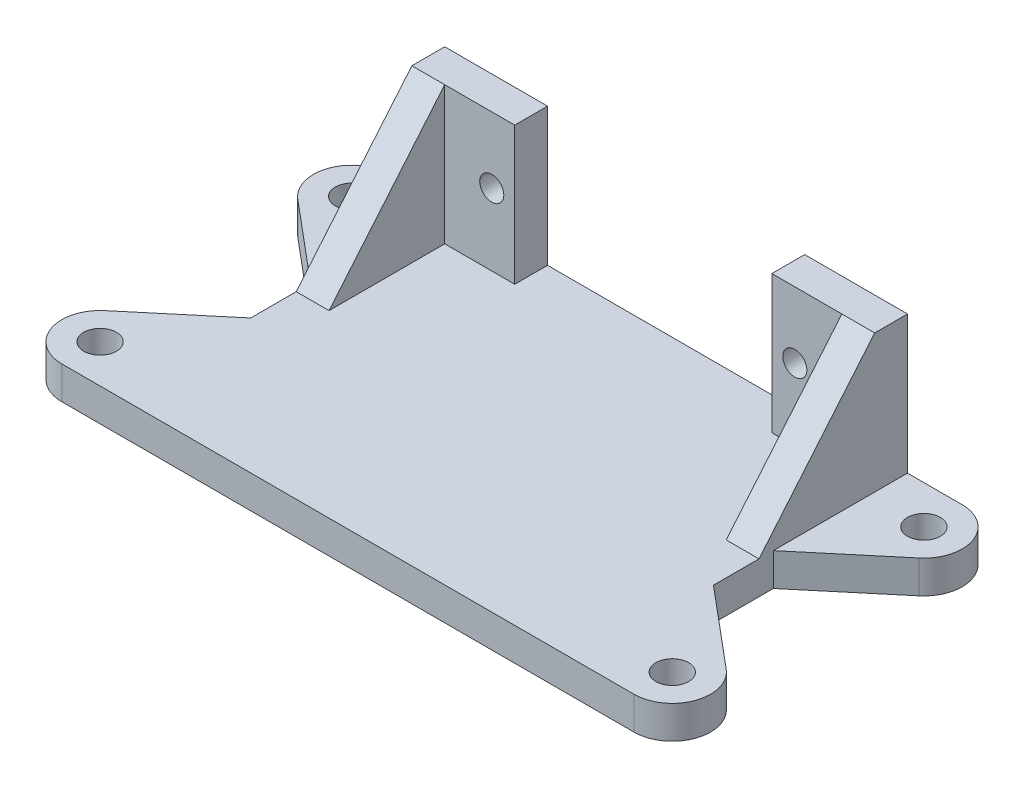
SolidWorks part; units mm, degrees
material "ABS"
ref_plane "Front Plane" through (0, 0, 0) normal (0, 0, 1) x (1, 0, 0)
ref_plane "Top Plane" through (0, 0, 0) normal (0, 1, 0) x (1, 0, 0)
ref_plane "Right Plane" through (0, 0, 0) normal (1, 0, 0) x (0, 0, -1)
sketch "Sketch2" plane through (0, 0, 0) normal (0, 0, 1) x (1, 0, 0)
  line L0 (-11.75, 3) -> (11.75, 3)
  line L1 (-16.15, 3.5) -> (16.15, 3.5) construction
  line L2 (-16.15, 3.5) -> (-16.15, 15.6) construction
  line L3 (-16.15, 15.6) -> (16.15, 15.6) construction
  line L4 (16.15, 3.5) -> (16.15, 15.6) construction
  line L5 (-11.25, 3.5) -> (11.25, 3.5) construction
  line L6 (-11.25, 3.5) -> (-11.25, 15.6) construction
  line L7 (-11.25, 15.6) -> (11.25, 15.6) construction
  line L8 (11.25, 3.5) -> (11.25, 15.6) construction
  line L9 (11.75, 3) -> (11.75, 15.6)
  line L10 (11.75, 15.6) -> (21.15, 15.6)
  line L11 (21.15, 15.6) -> (21.15, 0)
  line L12 (21.15, 0) -> (-21.15, 0)
  line L13 (-21.15, 0) -> (-21.15, 15.6)
  line L14 (-21.15, 15.6) -> (-11.75, 15.6)
  line L15 (-11.75, 15.6) -> (-11.75, 3)
  point P10 (0, 3.5)
  point P17 (0, 3)
  dimension "D1" = 32.3
  dimension "D2" = 12.1
  dimension "D3" = 22.5
  dimension "D4" = 0.5
  dimension "D5" = 0.5
  dimension "D6" = 3
  dimension "D7" = 5
extrude "Boss-Extrude1" add sketch "Sketch2" along normal blind 3 contours L11 L12 L13 L14 L15 L0 L9 L10
sketch "Sketch3" plane through (0, 0, 0) normal (0, -1, 0) x (1, 0, 0)
  line L1 (-21.15, 0) -> (21.15, 0)
  line L2 (-21.15, 0) -> (-21.15, 30)
  line L3 (-21.15, 30) -> (21.15, 30)
  line L4 (21.15, 0) -> (21.15, 30)
  dimension "D1" = 30
extrude "Boss-Extrude2" add sketch "Sketch3" against normal up to surface (3 mm away) up to face at (0, 3, 1.5)
sketch "Sketch4" plane through (0, 0, 3) normal (0, 0, 1) x (1, 0, 0)
  line L0 (-13.85, 9.55) -> (13.85, 9.55) construction
  line L1 (-21.15, 15.6) -> (-11.75, 15.6) construction
  line L2 (-16.15, 15.6) -> (16.15, 15.6) construction
  line L3 (-16.15, 15.6) -> (-16.15, 3.5) construction
  line L4 (-16.15, 3.5) -> (16.15, 3.5) construction
  line L5 (16.15, 15.6) -> (16.15, 3.5) construction
  line L6 (16.15, 9.55) -> (13.85, 9.55) construction
  circle A0 centre (13.85, 9.55) radius 1.1
  circle A1 centre (-13.85, 9.55) radius 1.1
  point P4 (0, 9.55)
  point P12 (0, 3.5)
  dimension "D1" = 2.2
  dimension "D2" = 27.7
  dimension "D3" = 32.3
  dimension "D4" = 12.1
extrude "Cut-Extrude1" cut sketch "Sketch4" against normal through all
sketch "Sketch5" plane through (21.15, 0, 0) normal (1, 0, 0) x (0, 0, -1)
  line L0 (-3, 15.6) -> (-13.5727, 3)
  line L1 (-3, 3) -> (-30, 3) construction
  line L2 (-13.5727, 3) -> (-3, 3)
  line L3 (-3, 15.6) -> (-3, 3) construction
  line L4 (-3, 3) -> (-3, 15.6)
  dimension "D1" = 40
extrude "Boss-Extrude3" add sketch "Sketch5" against normal blind 3
ref_plane "Plane1" through (0, 0, 0) normal (1, 0, 0) x (0, 0, -1)
mirror "Mirror1" about plane through (0, 0, 0) normal (1, 0, 0) of "Boss-Extrude3"
sketch "Sketch6" plane through (0, 0, 0) normal (0, -1, 0) x (1, 0, 0)
  line L0 (-21.15, 30) -> (-26.15, 30)
  line L1 (-28.3998, 23.8188) -> (-21.15, 17.7356)
  line L2 (-21.15, 30) -> (-21.15, 0) construction
  line L3 (-21.15, 30) -> (-21.15, 17.7356)
  arc A0 (-26.15, 30) -> (-28.3998, 23.8188) centre (-26.15, 26.5) ccw
  circle A1 centre (-26.15, 26.5) radius 1.5
  dimension "D1" = 3
  dimension "D2" = 2
  dimension "D3" = 5
  dimension "D4" = 50
extrude "Boss-Extrude4" add sketch "Sketch6" against normal up to surface (3 mm away) up to face at (0, 3, 10.5242)
ref_plane "Plane2" through (0, 0, 15) normal (0, 0, 1) x (1, 0, 0)
mirror "Mirror2" about plane through (0, 0, 15) normal (0, 0, 1) of "Boss-Extrude4"
mirror "Mirror3" about plane through (0, 0, 0) normal (1, 0, 0) of "Mirror2", "Boss-Extrude4"
